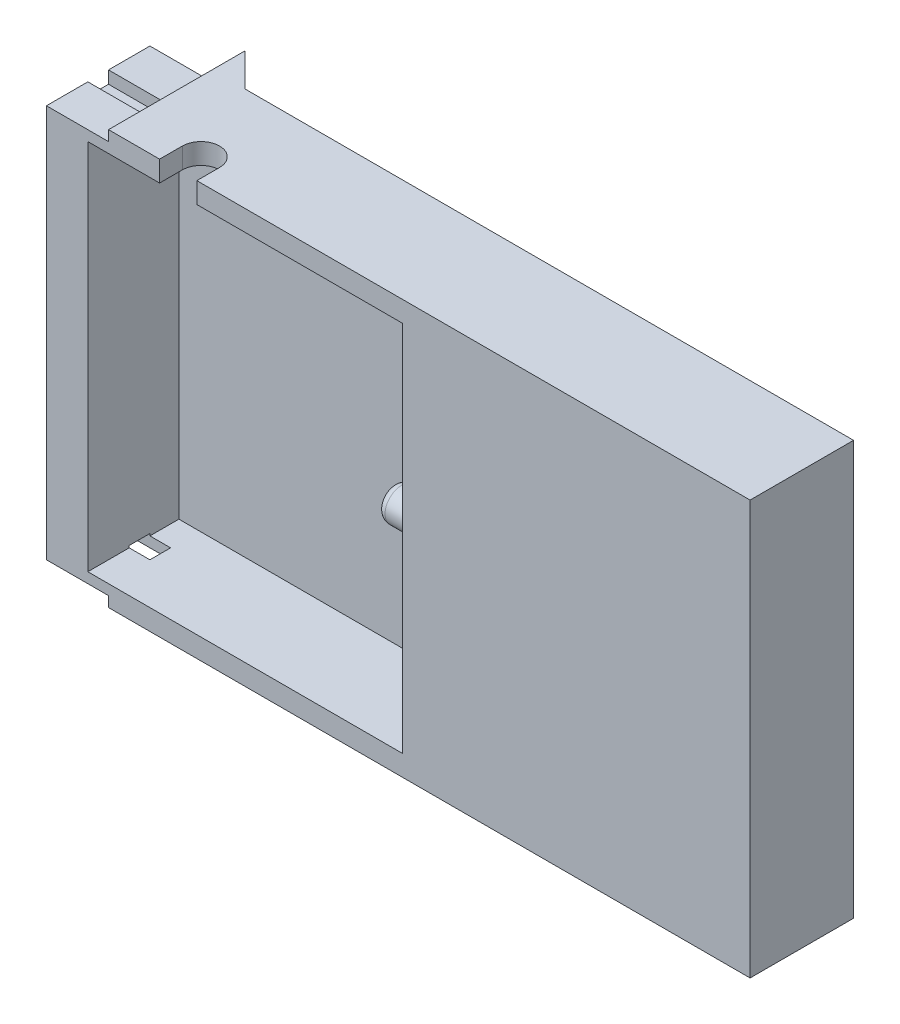
SolidWorks part; units mm, degrees
ref_plane "Front Plane" through (0, 0, 0) normal (0, 0, 1) x (1, 0, 0)
ref_plane "Top Plane" through (0, 0, 0) normal (0, 1, 0) x (1, 0, 0)
ref_plane "Right Plane" through (0, 0, 0) normal (1, 0, 0) x (0, 0, -1)
sketch "Sketch1" plane through (0, 0, 0) normal (0, 0, 1) x (1, 0, 0)
  line L1 (-101.108, 52.0776) -> (68.892, 52.0776)
  line L2 (-101.108, 52.0776) -> (-101.108, -47.9224)
  line L3 (-101.108, -47.9224) -> (68.892, -47.9224)
  line L4 (68.892, 52.0776) -> (68.892, -47.9224)
  dimension "D1" = 100
  dimension "D2" = 170
extrude "Boss-Extrude1" add sketch "Sketch1" along normal blind 15
sketch "Sketch2" plane through (0, 0, 0) normal (0, 0, -1) x (-1, 0, 0)
  line L1 (-58.892, 37.0776) -> (11.108, 37.0776)
  line L2 (-58.892, 37.0776) -> (-58.892, -32.9224)
  line L3 (-58.892, -32.9224) -> (11.108, -32.9224)
  line L4 (11.108, 37.0776) -> (11.108, -32.9224)
  line L5 (-58.892, 37.0776) -> (11.108, -32.9224) construction
  line L6 (-58.892, -32.9224) -> (11.108, 37.0776) construction
  line L7 (-68.892, 52.0776) -> (101.108, 52.0776) construction
  line L8 (101.108, -47.9224) -> (-68.892, -47.9224) construction
  line L9 (-68.892, -47.9224) -> (-68.892, 52.0776) construction
  point P0 (-23.892, 2.0776)
  dimension "D1" = 70
  dimension "D2" = 15
  dimension "D3" = 15
  dimension "D4" = 70
  dimension "D5" = 10
extrude "Cut-Extrude1" cut sketch "Sketch2" against normal blind 13
sketch "Sketch3" plane through (0, 0, 15) normal (0, 0, 1) x (1, 0, 0)
  line L0 (68.892, -47.9224) -> (68.892, 52.0776) construction
  line L9 (-91.108, 47.0776) -> (58.892, 47.0776)
  line L10 (-91.108, 47.0776) -> (-91.108, -42.9224)
  line L11 (-91.108, -42.9224) -> (58.892, -42.9224)
  line L12 (58.892, 47.0776) -> (58.892, -42.9224)
  line L13 (-101.108, 52.0776) -> (-101.108, -47.9224) construction
  line L14 (68.892, 52.0776) -> (-101.108, 52.0776) construction
  line L15 (-101.108, -47.9224) -> (68.892, -47.9224) construction
  line L17 (-91.108, 47.0776) -> (-21.108, 47.0776)
  line L18 (-91.108, 47.0776) -> (-91.108, -42.9224)
  line L19 (-91.108, -42.9224) -> (-21.108, -42.9224)
  line L20 (-21.108, 47.0776) -> (-21.108, -42.9224)
  dimension "D1" = 150
  dimension "D2" = 10
  dimension "D3" = 10
  dimension "D4" = 90
  dimension "D5" = 5
  dimension "D6" = 5
  dimension "D7" = 80
extrude "Cut-Extrude2" cut sketch "Sketch3" against normal blind 12 contours L20 L9 L10 L11 region at (-56.108, 2.0776, 15)
sketch "Sketch8" plane through (0, 52.0776, 0) normal (0, 1, 0) x (1, 0, 0)
  line L0 (68.892, -15) -> (-101.108, -15) construction
  line L1 (-101.108, 0) -> (-86.108, 0)
  line L2 (-101.108, 0) -> (-101.108, -15)
  line L3 (-101.108, -15) -> (-86.108, -15)
  line L4 (-86.108, 0) -> (-86.108, -15)
  dimension "D1" = 15
extrude "Cut-Extrude9" cut sketch "Sketch8" against normal blind 2.5
sketch "Sketch9" plane through (0, -47.9224, 0) normal (0, -1, 0) x (1, 0, 0)
  line L0 (-101.108, 0) -> (68.892, 0) construction
  line L1 (-101.108, 15) -> (-86.108, 15)
  line L2 (-101.108, 15) -> (-101.108, 0)
  line L3 (-101.108, 0) -> (-86.108, 0)
  line L4 (-86.108, 15) -> (-86.108, 0)
  dimension "D1" = 15
extrude "Cut-Extrude10" cut sketch "Sketch9" against normal blind 2.5
sketch "Sketch10" plane through (-21.108, 0, 0) normal (-1, 0, 0) x (0, 0, 1)
  line L4 (15, -42.9224) -> (15, 47.0776)
  line L5 (15, -42.9224) -> (15, 47.0776)
  line L6 (15, 47.0776) -> (3, 47.0776)
  line L7 (15, 47.0776) -> (3, 47.0776)
  line L8 (3, 47.0776) -> (3, -42.9224)
  line L9 (3, 47.0776) -> (3, -42.9224)
  line L10 (3, -42.9224) -> (15, -42.9224)
  line L11 (3, -42.9224) -> (15, -42.9224)
  dimension "D1" = 0
extrude "Cut-Extrude11" cut sketch "Sketch10" against normal blind 10
sketch "Sketch11" plane through (0, 0, 15) normal (0, 0, 1) x (1, 0, 0)
  line L0 (-91.108, -42.9224) -> (-11.108, -42.9224) construction
  line L1 (-11.108, -42.9224) -> (-11.108, 47.0776) construction
  line L2 (-91.108, 47.0776) -> (-11.108, 47.0776) construction
  line L3 (-91.108, 47.0776) -> (-91.108, -42.9224) construction
  line L4 (-91.108, -42.9224) -> (-11.108, -42.9224)
  line L5 (-11.108, -42.9224) -> (-11.108, 47.0776)
  line L6 (-91.108, 47.0776) -> (-11.108, 47.0776)
  line L7 (-91.108, 47.0776) -> (-91.108, -42.9224)
  line L8 (-86.108, -45.4224) -> (-86.108, -47.9224)
  line L9 (-86.108, -47.9224) -> (68.892, -47.9224)
  line L10 (68.892, -47.9224) -> (68.892, 52.0776)
  line L11 (68.892, 52.0776) -> (-86.108, 52.0776)
  line L12 (-86.108, 52.0776) -> (-86.108, 49.5776)
  line L13 (-86.108, 49.5776) -> (-101.108, 49.5776)
  line L14 (-101.108, 49.5776) -> (-101.108, -45.4224)
  line L15 (-101.108, -45.4224) -> (-86.108, -45.4224)
  line L16 (-86.108, -45.4224) -> (-86.108, -47.9224)
  line L17 (-86.108, -47.9224) -> (68.892, -47.9224)
  line L18 (68.892, -47.9224) -> (68.892, 52.0776)
  line L19 (68.892, 52.0776) -> (-86.108, 52.0776)
  line L20 (-86.108, 52.0776) -> (-86.108, 49.5776)
  line L21 (-86.108, 49.5776) -> (-101.108, 49.5776)
  line L22 (-101.108, 49.5776) -> (-101.108, -45.4224)
  line L23 (-101.108, -45.4224) -> (-86.108, -45.4224)
  dimension "D1" = 0
extrude "Boss-Extrude2" add sketch "Sketch11" along normal blind 10
sketch "Sketch12" plane through (-11.108, 0, 0) normal (-1, 0, 0) x (0, 0, 1)
  line L5 (3, 47.0776) -> (25, 47.0776)
  line L6 (3, 47.0776) -> (3, -42.9224)
  line L7 (3, -42.9224) -> (25, -42.9224)
  line L8 (25, 47.0776) -> (25, -42.9224)
extrude "Boss-Extrude4" add sketch "Sketch12" along normal blind 4
extrude "Cut-Extrude12" cut sketch "Sketch2<2>" against normal blind 22
sketch "Sketch2<2>" plane through (0, 0, 0) normal (0, 0, -1) x (-1, 0, 0) same geometry as "Sketch2"
sketch "Sketch13" plane through (0, 0, 0) normal (0, 0, -1) x (-1, 0, 0)
  line L0 (11.108, -32.9224) -> (11.108, 37.0776) construction
  line L1 (11.108, -32.9224) -> (11.108, 37.0776)
  line L2 (-58.892, -32.9224) -> (11.108, -32.9224) construction
  line L3 (-58.892, 37.0776) -> (-58.892, -32.9224) construction
  line L4 (11.108, 37.0776) -> (-58.892, 37.0776) construction
  line L5 (-58.892, -32.9224) -> (11.108, -32.9224)
  line L6 (-58.892, 37.0776) -> (-58.892, -32.9224)
  line L7 (11.108, 37.0776) -> (-58.892, 37.0776)
  line L9 (-60.892, 39.0776) -> (13.108, 39.0776)
  line L10 (-60.892, 39.0776) -> (-60.892, -34.9224)
  line L11 (-60.892, -34.9224) -> (13.108, -34.9224)
  line L12 (13.108, 39.0776) -> (13.108, -34.9224)
  dimension "D1" = 2
  dimension "D2" = 2
  dimension "D3" = 2
  dimension "D4" = 2
extrude "Cut-Extrude13" cut sketch "Sketch13" against normal blind 4
sketch "Sketch14" plane through (0, 52.0776, 0) normal (0, 1, 0) x (1, 0, 0)
  line L0 (-86.108, 0) -> (-78.108, 0)
  line L1 (68.892, 0) -> (-86.108, 0) construction
  line L2 (-78.108, 0) -> (-86.108, 8)
  line L3 (-86.108, -21) -> (-86.108, 55) construction
  line L4 (-86.108, 8) -> (-86.108, 0)
  dimension "D1" = 8
  dimension "D2" = 8
extrude "Boss-Extrude6" add sketch "Sketch14" against normal blind 100
sketch "Sketch15" plane through (-101.108, 0, 0) normal (-1, 0, 0) x (0, 0, 1)
  line L5 (12.5, -45.4224) -> (12.5, 49.5776) construction
  line L6 (0, -45.4224) -> (25, -45.4224)
  line L8 (0, -45.4224) -> (0, 49.5776)
  line L9 (0, 49.5776) -> (25, 49.5776)
  line L10 (25, -45.4224) -> (25, 49.5776)
  line L17 (10, -45.4224) -> (10, -42.4224)
  line L18 (10, -42.4224) -> (15, -42.4224)
  line L19 (15, -45.4224) -> (15, -42.4224)
  line L20 (12.5, -45.4224) -> (15, -42.4224) construction
  line L21 (10, -42.4224) -> (12.5, -45.4224) construction
  line L22 (10, 46.5776) -> (15, 46.5776)
  line L23 (10, 46.5776) -> (10, 49.5776)
  line L25 (15, 46.5776) -> (15, 49.5776)
  line L26 (10, 46.5776) -> (12.5, 49.5776) construction
  line L27 (12.5, 49.5776) -> (15, 46.5776) construction
  point P12 (10, 48.0776)
  dimension "D1" = 5
  dimension "D2" = 3
  dimension "D3" = 5
  dimension "D4" = 2.5
  dimension "D5" = 2.5
  dimension "D6" = 3
extrude "Cut-Extrude14" cut sketch "Sketch15" against normal blind 15 contours L22 L25 L9 L23 | L6 L19 L18 L17 region at (-101.108, -43.9224, 12.5) region at (-101.108, 48.0776, 12.5)
sketch "Sketch16" plane through (-11.108, 0, 0) normal (1, 0, 0) x (0, 0, -1)
  circle A0 centre (-15.9201, 0) radius 3
  circle A1 centre (-15.9201, 0) radius 4
extrude "Boss-Extrude7" add sketch "Sketch16" against normal blind 15
extrude "Cut-Extrude15" cut sketch "Sketch16<3>" against normal blind 15 contours A0
sketch "Sketch16<3>" plane through (-11.108, 0, 0) normal (1, 0, 0) x (0, 0, -1) same geometry as "Sketch16"
fillet "Fillet1" radius 2 1 edges at (-26.108, 4, 15.9201)
sketch "Sketch17" plane through (0, 52.0776, 0) normal (0, 1, 0) x (1, 0, 0)
  line L0 (-64.7716, -19.5062) -> (-64.7716, -25)
  line L1 (68.892, -25) -> (-86.108, -25) construction
  line L2 (-73.77, -19.5062) -> (-73.77, -25)
  arc A0 (-64.7716, -19.5062) -> (-73.77, -19.5062) centre (-69.2708, -19.5062) ccw
  point P8 (0, 0)
  point P9 (-69.2708, -19.5062)
extrude "Cut-Extrude16" cut sketch "Sketch17" against normal blind 15 and the other way through all
